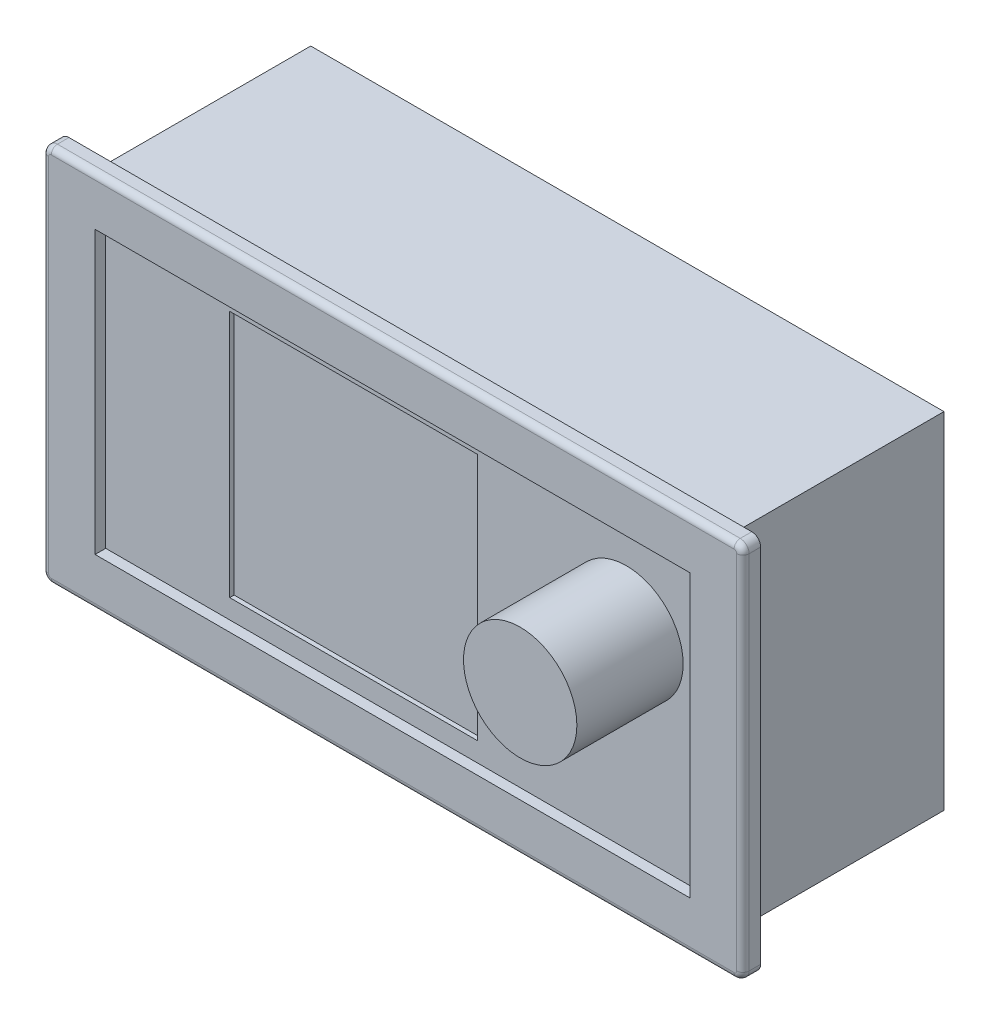
SolidWorks part; units mm, degrees
ref_plane "Спереди" through (0, 0, 0) normal (0, 0, 1) x (1, 0, 0)
ref_plane "Сверху" through (0, 0, 0) normal (0, 1, 0) x (1, 0, 0)
ref_plane "Справа" through (0, 0, 0) normal (1, 0, 0) x (0, 0, -1)
sketch "Эскиз1" plane through (0, 0, 0) normal (0, 0, 1) x (1, 0, 0)
  line L1 (-35.75, 19.5) -> (35.75, 19.5)
  line L2 (-35.75, 19.5) -> (-35.75, -19.5)
  line L3 (-35.75, -19.5) -> (35.75, -19.5)
  line L4 (35.75, 19.5) -> (35.75, -19.5)
  line L5 (-35.75, 19.5) -> (35.75, -19.5) construction
  line L6 (-35.75, -19.5) -> (35.75, 19.5) construction
  point P0 (0, 0)
  dimension "D1" = 39
  dimension "D2" = 71.5
extrude "Бобышка-Вытянуть1" add sketch "Эскиз1" along normal blind 24.5
sketch "Эскиз2" plane through (0, 0, 24.5) normal (0, 0, 1) x (1, 0, 0)
  line L1 (-39.55, 21.4) -> (39.55, 21.4)
  line L2 (-39.55, 21.4) -> (-39.55, -21.4)
  line L3 (-39.55, -21.4) -> (39.55, -21.4)
  line L4 (39.55, 21.4) -> (39.55, -21.4)
  line L5 (-39.55, 21.4) -> (39.55, -21.4) construction
  line L6 (-39.55, -21.4) -> (39.55, 21.4) construction
  point P0 (0, 0)
  dimension "D1" = 42.8
  dimension "D2" = 79.1
extrude "Бобышка-Вытянуть2" add sketch "Эскиз2" along normal blind 2
fillet "Скругление1" radius 0.7 4 edges at (0, -21.4, 26.5) (-39.55, 0, 26.5) (0, 21.4, 26.5) (39.55, 0, 26.5)
fillet "Скругление2" radius 1 8 edges at (-39.345, 21.195, 26.295) (39.345, 21.195, 26.295) (39.345, -21.195, 26.295) (-39.345, -21.195, 26.295) (-39.55, -21.4, 25.15) (39.55, -21.4, 25.15) (39.55, 21.4, 25.15) (-39.55, 21.4, 25.15)
sketch "Эскиз3" plane through (0, 0, 26.5) normal (0, 0, 1) x (1, 0, 0)
  line L1 (-33.6, 15.9) -> (33.6, 15.9)
  line L2 (-33.6, 15.9) -> (-33.6, -15.9)
  line L3 (-33.6, -15.9) -> (33.6, -15.9)
  line L4 (33.6, 15.9) -> (33.6, -15.9)
  line L5 (-33.6, 15.9) -> (33.6, -15.9) construction
  line L6 (-33.6, -15.9) -> (33.6, 15.9) construction
  point P0 (0, 0)
  dimension "D1" = 31.8
  dimension "D2" = 67.2
extrude "Вырез-Вытянуть1" cut sketch "Эскиз3" against normal blind 1.2
sketch "Эскиз4" plane through (0, 0, 25.3) normal (0, 0, 1) x (1, 0, 0)
  line L0 (33.6, -15.9) -> (33.6, 15.9) construction
  line L1 (33.6, 15.9) -> (-33.6, 15.9) construction
  circle A0 centre (25.2, 5.4) radius 6.4
  point P2 (0, 0)
  dimension "D1" = 12.8
  dimension "D2" = 8.4
  dimension "D3" = 10.5
extrude "Бобышка-Вытянуть3" add sketch "Эскиз4" along normal blind 12
sketch "Эскиз5" plane through (0, 0, 25.3) normal (0, 0, 1) x (1, 0, 0)
  line L0 (-33.6, 15.9) -> (-33.6, -15.9) construction
  line L1 (-19.6, 14.2825) -> (8.4, 14.2825)
  line L2 (-19.6, 14.2825) -> (-19.6, -13.7175)
  line L3 (-19.6, -13.7175) -> (8.4, -13.7175)
  line L4 (8.4, 14.2825) -> (8.4, -13.7175)
  line L5 (-19.6, 14.2825) -> (8.4, -13.7175) construction
  line L6 (-19.6, -13.7175) -> (8.4, 14.2825) construction
  point P0 (-5.6, 0.2825)
  dimension "D1" = 28
  dimension "D2" = 28
  dimension "D3" = 14
extrude "Вырез-Вытянуть2" cut sketch "Эскиз5" against normal blind 0.5
